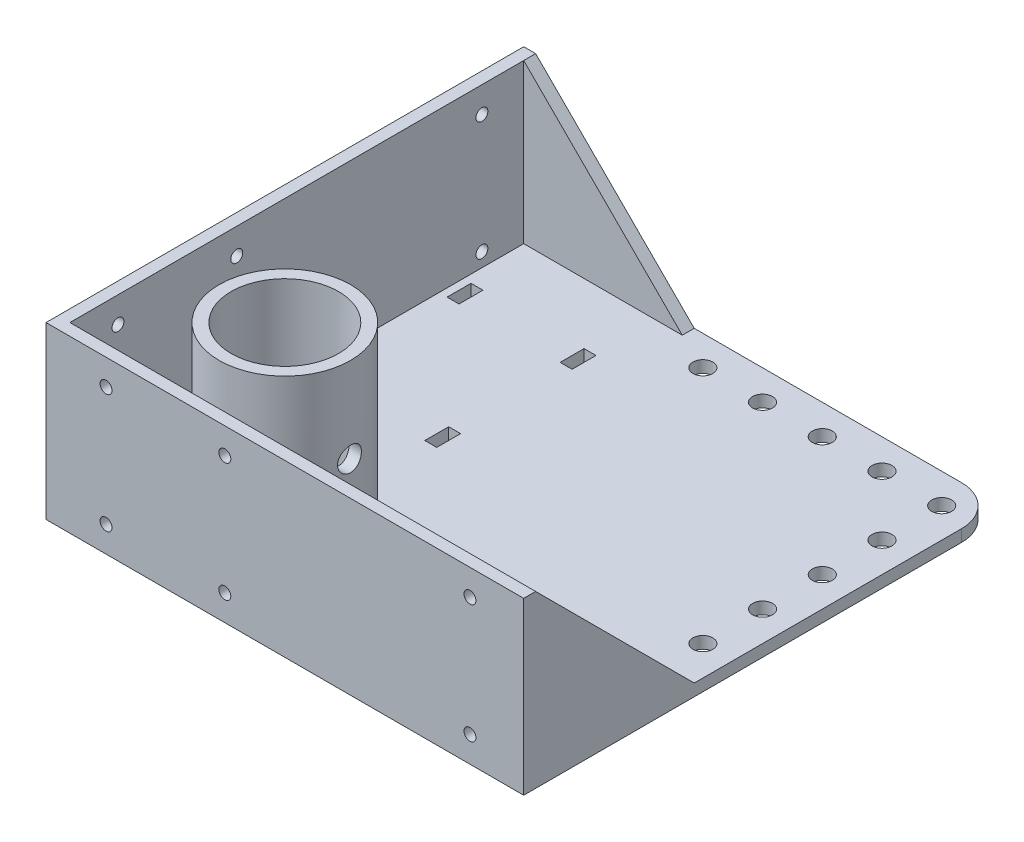
SolidWorks part; units mm, degrees
ref_plane "Front Plane" through (0, 0, 0) normal (0, 0, 1) x (1, 0, 0)
ref_plane "Top Plane" through (0, 0, 0) normal (0, 1, 0) x (1, 0, 0)
ref_plane "Right Plane" through (0, 0, 0) normal (1, 0, 0) x (0, 0, -1)
sketch "Sketch1" plane through (0, 0, 0) normal (0, 1, 0) x (1, 0, 0)
  line L0 (-30, -30) -> (90, 90) construction
  line L1 (-30, -30) -> (90, -30)
  line L2 (-30, -30) -> (-30, 90)
  line L3 (-30, 90) -> (90, 90)
  line L4 (90, -30) -> (90, 90)
  dimension "D1" = 120
  dimension "D2" = 30
extrude "Boss-Extrude1" add sketch "Sketch1" against normal blind 3
sketch "Sketch2" plane through (0, 0, 0) normal (0, 1, 0) x (1, 0, 0)
  line L0 (-30, 90) -> (-27, 90)
  line L1 (90, 90) -> (-30, 90) construction
  line L2 (-27, 90) -> (-27, -27)
  line L3 (-27, -27) -> (90, -27)
  line L4 (90, -30) -> (90, 90) construction
  line L5 (90, -27) -> (90, -30)
  line L6 (90, -30) -> (-30, -30)
  line L7 (-30, -30) -> (-30, 90)
  dimension "D1" = 3
extrude "Boss-Extrude2" add sketch "Sketch2" along normal blind 42.84 from surface starting at face at (30, -3, -30)
sketch "Sketch6" plane through (0, 0, 30) normal (0, 0, 1) x (1, 0, 0)
  line L0 (-14.92, 33.34) -> (14.92, 3.5) construction
  line L1 (14.92, 33.34) -> (-14.92, 3.5) construction
  line L2 (-30, -3) -> (-30, 39.84) construction
  line L3 (90, 39.84) -> (-30, 39.84) construction
  circle A0 centre (-14.92, 33.34) radius 1.5
  circle A1 centre (14.92, 33.34) radius 1.5
  circle A2 centre (14.92, 3.5) radius 1.5
  circle A3 centre (-14.92, 3.5) radius 1.5
  circle A4 centre (76.5, 33.34) radius 1.5
  circle A5 centre (76.5, 3.5) radius 1.5
  point P4 (0, 18.42)
  point P8 (-30, 18.42)
  point P19 (0, 0)
  point P20 (0, 0)
  point P21 (0, 0)
  dimension "D3" = 3
  dimension "D1" = 42.2
  dimension "D2" = 45
  dimension "D4" = 61.58
extrude "Cut-Extrude1" cut sketch "Sketch6" against normal through all
ref_plane "Plane1" through (0, 0, 0) normal (-0.7071, 0, -0.7071) x (-0.7071, 0, 0.7071)
mirror "Mirror1" about plane through (0, 0, 0) normal (-0.7071, 0, -0.7071) of "Cut-Extrude1"
sketch "Sketch3" plane through (90, 0, 0) normal (1, 0, 0) x (0, 0, -1)
  line L0 (-27, 39.84) -> (-27, 0)
  line L1 (-27, 0) -> (12.84, 0)
  line L2 (-27, 0) -> (90, 0) construction
  line L3 (12.84, 0) -> (-27, 39.84)
extrude "Boss-Extrude3" add sketch "Sketch3" against normal blind 3
sketch "Sketch7" plane through (0, 0, 0) normal (0, 1, 0) x (1, 0, 0)
  circle A0 centre (0, 0) radius 13.5
  dimension "D1" = 27
extrude "Cut-Extrude2" cut sketch "Sketch7" against normal through all
sketch "Sketch8" plane through (0, 0, 0) normal (0, 1, 0) x (1, 0, 0)
  circle A0 centre (0, 0) radius 13.5 construction
  circle A1 centre (0, 0) radius 13.5
  circle A2 centre (0, 0) radius 16.5
  dimension "D1" = 3
extrude "Boss-Extrude5" add sketch "Sketch8" along normal through all
sketch "Sketch9" plane through (0, 0, 0) normal (1, 0, 0) x (0, 0, -1)
  line L0 (0, 39.84) -> (0, -3) construction
  line L1 (13.5, 39.84) -> (-13.5, 39.84) construction
  line L2 (-30, -3) -> (90, -3) construction
  circle A0 centre (0, 18.42) radius 3
  dimension "D1" = 6
extrude "Cut-Extrude3" cut sketch "Sketch9" along normal through all
sketch "Sketch10" plane through (0, 0, 0) normal (0, 1, 0) x (1, 0, 0)
  line L0 (37.75, 3.4) -> (65.75, -22) construction
  line L5 (31.75, 3.4) -> (37.75, 3.4)
  line L6 (31.75, 3.4) -> (31.75, 6.4)
  line L7 (31.75, 6.4) -> (37.75, 6.4)
  line L8 (37.75, 3.4) -> (37.75, 6.4)
  line L9 (71.75, 3.4) -> (65.75, 3.4)
  line L10 (71.75, 3.4) -> (71.75, 6.4)
  line L11 (71.75, 6.4) -> (65.75, 6.4)
  line L12 (65.75, 3.4) -> (65.75, 6.4)
  line L13 (71.75, -22) -> (65.75, -22)
  line L14 (71.75, -22) -> (71.75, -25)
  line L15 (71.75, -25) -> (65.75, -25)
  line L16 (65.75, -22) -> (65.75, -25)
  line L17 (31.75, -22) -> (37.75, -22)
  line L18 (31.75, -22) -> (31.75, -25)
  line L19 (31.75, -25) -> (37.75, -25)
  line L20 (37.75, -22) -> (37.75, -25)
  line L21 (21.75, 3.4) -> (81.75, 3.4) construction
  line L22 (21.75, 3.4) -> (21.75, -22) construction
  line L23 (21.75, -22) -> (81.75, -22) construction
  line L24 (81.75, 3.4) -> (81.75, -22) construction
  line L25 (-27, -27) -> (87, -27) construction
  line L27 (16.5, 0) -> (21.75, 0) construction
  line L28 (81.75, -9.3) -> (87, -9.3) construction
  line L29 (87, 12.84) -> (87, -27) construction
  line L30 (90, 90) -> (-30, -30) construction
  line L31 (90, 12.84) -> (90, 90) construction
  circle A0 centre (0, 0) radius 16.5 construction
  circle A1 centre (0, 0) radius 16.5 construction
  circle A2 centre (82.5, 82.5) radius 2.5
  circle A3 centre (82.5, 67.5) radius 2.5
  circle A4 centre (82.5, 52.5) radius 2.5
  circle A5 centre (82.5, 37.5) radius 2.5
  circle A6 centre (82.5, 22.5) radius 2.5
  point P20 (51.75, -9.3)
  point P21 (51.75, 3.4)
  point P44 (0, 0)
  point P52 (0, 0)
  dimension "D8" = 5
  dimension "D1" = 3
  dimension "D2" = 6
  dimension "D3" = 10
  dimension "D4" = 60
  dimension "D5" = 2
  dimension "D6" = 7.5
  dimension "D7" = 25.4
  dimension "D9" = 15
extrude "Cut-Extrude4" cut sketch "Sketch10" against normal through all
mirror "Mirror2" about plane through (0, 0, 0) normal (-0.7071, 0, -0.7071) of "Cut-Extrude4", "Boss-Extrude3", "Cut-Extrude3"
fillet "Fillet1" radius 10 1 edges at (90, -1.5, -90)
